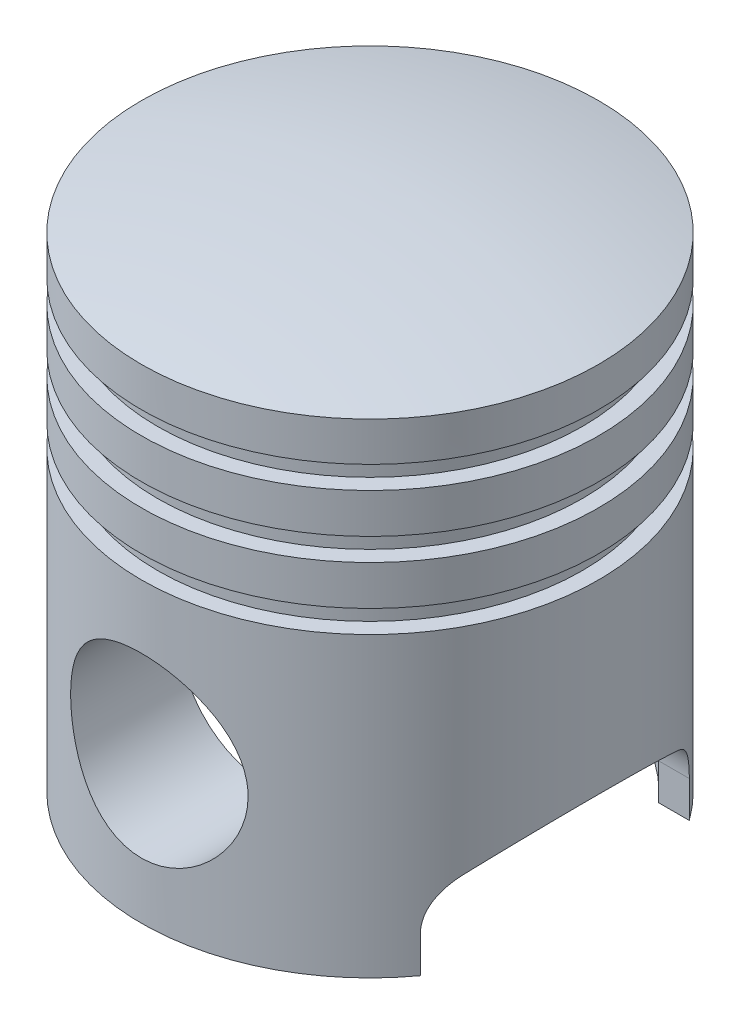
SolidWorks part; units mm, degrees
material "6061-T6 (SS)"
ref_plane "Front Plane" through (0, 0, 0) normal (0, 0, 1) x (1, 0, 0)
ref_plane "Top Plane" through (0, 0, 0) normal (0, 1, 0) x (1, 0, 0)
ref_plane "Right Plane" through (0, 0, 0) normal (1, 0, 0) x (0, 0, -1)
sketch "Sketch3" plane through (0, 0, 0) normal (0, 1, 0) x (1, 0, 0)
  circle A0 centre (0, 0) radius 42.5
  dimension "D1" = 85
extrude "Boss-Extrude1" add sketch "Sketch3" along normal blind 90
sketch "Sketch4" plane through (0, 0, 0) normal (0, 0, 1) x (1, 0, 0)
  line L1 (42.5, 90) -> (-42.5, 90) construction
  line L2 (0, 95) -> (0, 90)
  line L3 (0, 90) -> (42.5, 90)
  arc A0 (-42.5, 90) -> (42.5, 90) centre (0, -88.125) cw
  point P3 (0, 95)
  dimension "D1" = 5
revolve "Revolve1" [suppressed] add sketch "Sketch4" angle 360 about L2
sketch "Sketch8" plane through (0, 90, 0) normal (0, 1, 0) x (1, 0, 0)
  circle A0 centre (0, 0) radius 39.5
  dimension "D1" = 79
extrude "Cut-Extrude5" cut sketch "Sketch8" against normal blind 4.2 from offset 7.3 flip side to cut offset against normal yes
dome "Dome1" faces to dome 1 distance 5 reverse direction no elliptical dome no face at (0, 90, 42.5) parameters "D1"=5
sketch "Sketch7" plane through (0, 0, 0) normal (0, 1, 0) x (1, 0, 0)
  circle A0 centre (0, 0) radius 38
  dimension "D1" = 76
extrude "Cut-Extrude4" cut sketch "Sketch7" along normal blind 85 contours A0 region at (0, 0, 0)
sketch "Sketch5" plane through (0, 0, 0) normal (0, 0, 1) x (1, 0, 0)
  circle A0 centre (0, 27) radius 16.5
  dimension "D1" = 33
  dimension "D2" = 27
extrude "Cut-Extrude1" cut sketch "Sketch5" against normal through all both and the other way through all
sketch "Sketch6" plane through (0, 0, 0) normal (1, 0, 0) x (0, 0, -1)
  line L0 (-25, 0) -> (25, 0)
  line L1 (-42.5, 0) -> (42.5, 0) construction
  line L2 (25, 0) -> (25, 12)
  line L3 (-25, 12) -> (-25, 0)
  arc A0 (25, 12) -> (-25, 12) centre (0, -19.225) ccw
  point P7 (0, 0)
  dimension "D4" = 40
  dimension "D1" = 50
  dimension "D2" = 12
  dimension "D3" = 12
extrude "Cut-Extrude2" cut sketch "Sketch6" against normal through all both and the other way through all
pattern_linear "LPattern1" count 3 spacing 11.6 along (0, -1, 0) of "Cut-Extrude5"
fillet "Fillet1" radius 10 4 edges at (-31.4937, 12, 25) (-31.4937, 12, -25) (31.4937, 12, -25) (31.4937, 12, 25)
sketch "Sketch9" plane through (0, 0, 0) normal (0, 0, 1) x (1, 0, 0)
  circle A0 centre (0, 27) radius 16.5 construction
  circle A1 centre (0, 27) radius 16.5
  circle A2 centre (0, 27) radius 22.5
  dimension "D1" = 45
extrude "Boss-Extrude2" add sketch "Sketch9" along normal up to surface (15.2308 mm away) from offset 19 up to face at (0, 8.2816, 0)
mirror "Mirror1" about plane through (0, 0, 0) normal (0, 0, 1) of "Boss-Extrude2"
